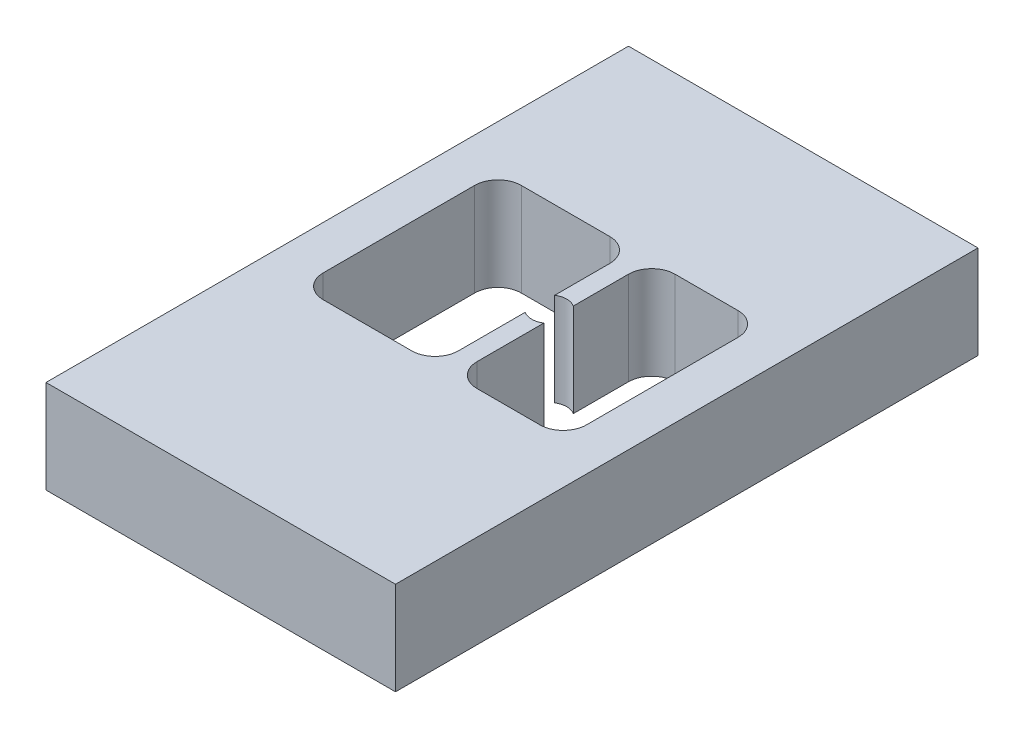
SolidWorks part; units mm, degrees
material "K110"
ref_plane "Front Plane" through (0, 0, 0) normal (0, 0, 1) x (1, 0, 0)
ref_plane "Top Plane" through (0, 0, 0) normal (0, 1, 0) x (1, 0, 0)
ref_plane "Right Plane" through (0, 0, 0) normal (1, 0, 0) x (0, 0, -1)
sketch "Sketch1" plane through (0, 0, 0) normal (0, 1, 0) x (1, 0, 0)
  line L1 (-75, 125) -> (75, 125)
  line L2 (-75, 125) -> (-75, -125)
  line L3 (-75, -125) -> (75, -125)
  line L4 (75, 125) -> (75, -125)
  line L5 (-75, 125) -> (75, -125) construction
  line L6 (-75, -125) -> (75, 125) construction
  point P0 (0, 0)
  dimension "D1" = 250
  dimension "D2" = 150
extrude "Boss-Extrude1" add sketch "Sketch1" against normal blind 40
sketch "Sketch2" plane through (0, 0, 0) normal (0, 1, 0) x (1, 0, 0)
  line L3 (24.75, -27.27) -> (24.75, -11.27) construction
  line L4 (27.75, -8.27) -> (33.88, -8.27) construction
  line L5 (35.88, -6.27) -> (35.88, 11.73) construction
  line L6 (33.88, 13.73) -> (27.75, 13.73) construction
  line L7 (24.75, 42.73) -> (24.75, 16.73) construction
  line L8 (-37.37, 42.73) -> (-13.25, 42.73) construction
  line L9 (-13.25, 42.73) -> (-13.25, 34.23) construction
  line L10 (-14.75, 32.73) -> (-29.37, 32.73) construction
  line L11 (-35.37, 26.73) -> (-35.37, -6.27) construction
  line L12 (-29.37, -12.27) -> (-14.75, -12.27) construction
  line L13 (-13.25, -27.27) -> (-13.25, -13.77) construction
  line L14 (-37.37, -27.27) -> (-13.25, -27.27) construction
  line L15 (-40.37, 39.73) -> (-40.37, -24.27) construction
  line L19 (24.75, -27.27) -> (24.75, -11.27)
  line L20 (27.75, -8.27) -> (33.88, -8.27)
  line L21 (35.88, -6.27) -> (35.88, 11.73)
  line L22 (33.88, 13.73) -> (27.75, 13.73)
  line L23 (24.75, 42.73) -> (24.75, 16.73)
  line L24 (-37.37, 42.73) -> (-13.25, 42.73)
  line L25 (-13.25, 42.73) -> (-13.25, 34.23)
  line L26 (-14.75, 32.73) -> (-29.37, 32.73)
  line L27 (-35.37, 26.73) -> (-35.37, -6.27)
  line L28 (-29.37, -12.27) -> (-14.75, -12.27)
  line L29 (-13.25, -27.27) -> (-13.25, -13.77)
  line L30 (-37.37, -27.27) -> (-13.25, -27.27)
  line L31 (-40.37, 39.73) -> (-40.37, -24.27)
  line L32 (40.88, 42.73) -> (40.88, 39.73) construction
  line L33 (37.88, 42.73) -> (40.88, 42.73) construction
  line L34 (40.88, -27.27) -> (37.88, -27.27) construction
  line L35 (40.88, -24.27) -> (40.88, -27.27) construction
  line L36 (24.75, 42.73) -> (37.88, 42.73) construction
  line L37 (40.88, 39.73) -> (40.88, -24.27) construction
  line L38 (37.88, -27.27) -> (24.75, -27.27) construction
  line L39 (24.75, 42.73) -> (37.88, 42.73)
  line L40 (40.88, 39.73) -> (40.88, -24.27)
  line L41 (37.88, -27.27) -> (24.75, -27.27)
  arc A0 (27.75, -8.27) -> (24.75, -11.27) centre (27.75, -11.27) ccw construction
  arc A1 (33.88, -8.27) -> (35.88, -6.27) centre (33.88, -6.27) ccw construction
  arc A2 (35.88, 11.73) -> (33.88, 13.73) centre (33.88, 11.73) ccw construction
  arc A3 (24.75, 16.73) -> (27.75, 13.73) centre (27.75, 16.73) ccw construction
  arc A4 (-37.37, 42.73) -> (-40.37, 39.73) centre (-37.37, 39.73) ccw construction
  arc A5 (-14.75, 32.73) -> (-13.25, 34.23) centre (-14.75, 34.23) ccw construction
  arc A6 (-29.37, 32.73) -> (-35.37, 26.73) centre (-29.37, 26.73) ccw construction
  arc A7 (-35.37, -6.27) -> (-29.37, -12.27) centre (-29.37, -6.27) ccw construction
  arc A8 (-13.25, -13.77) -> (-14.75, -12.27) centre (-14.75, -13.77) ccw construction
  arc A9 (-40.37, -24.27) -> (-37.37, -27.27) centre (-37.37, -24.27) ccw construction
  arc A10 (27.75, -8.27) -> (24.75, -11.27) centre (27.75, -11.27) ccw
  arc A11 (33.88, -8.27) -> (35.88, -6.27) centre (33.88, -6.27) ccw
  arc A12 (35.88, 11.73) -> (33.88, 13.73) centre (33.88, 11.73) ccw
  arc A13 (24.75, 16.73) -> (27.75, 13.73) centre (27.75, 16.73) ccw
  arc A14 (-37.37, 42.73) -> (-40.37, 39.73) centre (-37.37, 39.73) ccw
  arc A15 (-14.75, 32.73) -> (-13.25, 34.23) centre (-14.75, 34.23) ccw
  arc A16 (-29.37, 32.73) -> (-35.37, 26.73) centre (-29.37, 26.73) ccw
  arc A17 (-35.37, -6.27) -> (-29.37, -12.27) centre (-29.37, -6.27) ccw
  arc A18 (-13.25, -13.77) -> (-14.75, -12.27) centre (-14.75, -13.77) ccw
  arc A19 (-40.37, -24.27) -> (-37.37, -27.27) centre (-37.37, -24.27) ccw
  arc A20 (40.88, 39.73) -> (37.88, 42.73) centre (37.88, 39.73) ccw construction
  arc A21 (37.88, -27.27) -> (40.88, -24.27) centre (37.88, -24.27) ccw construction
  arc A22 (40.88, 39.73) -> (37.88, 42.73) centre (37.88, 39.73) ccw
  arc A23 (37.88, -27.27) -> (40.88, -24.27) centre (37.88, -24.27) ccw
sketch "Sketch3" plane through (0, 0, 0) normal (0, 1, 0) x (1, 0, 0)
  line L1 (-56.25, 50.23) -> (1.75, 50.23)
  line L2 (-56.25, 50.23) -> (-56.25, -34.77)
  line L3 (-56.25, -34.77) -> (1.75, -34.77)
  line L4 (1.75, 50.23) -> (1.75, -34.77)
  line L5 (9.75, 50.23) -> (56.75, 50.23)
  line L6 (9.75, 50.23) -> (9.75, -34.77)
  line L7 (9.75, -34.77) -> (56.75, -34.77)
  line L8 (56.75, 50.23) -> (56.75, -34.77)
  line L15 (24.75, 42.73) -> (24.75, 16.73) construction
  line L16 (-13.25, 42.73) -> (-13.25, 34.23) construction
  dimension "D1" = 85
  dimension "D4" = 15
  dimension "D5" = 15
  dimension "D6" = 47
  dimension "D7" = 58
extrude "Cut-Extrude1" cut sketch "Sketch3" against normal up to next
fillet "Fillet1" radius 10 8 edges at (9.75, -20, -50.23) (56.75, -20, 34.77) (56.75, -20, -50.23) (9.75, -20, 34.77) (-56.25, -20, 34.77) (1.75, -20, 34.77) (1.75, -20, -50.23) (-56.25, -20, -50.23)
extrude "Cut-Extrude4" cut sketch "Sketch7" against normal through all
sketch "Sketch7" plane through (269.63, 0, 0) normal (0, 1, 0) x (1, 0, 0)
  circle A0 centre (-263.88, 10.23) radius 7.5
